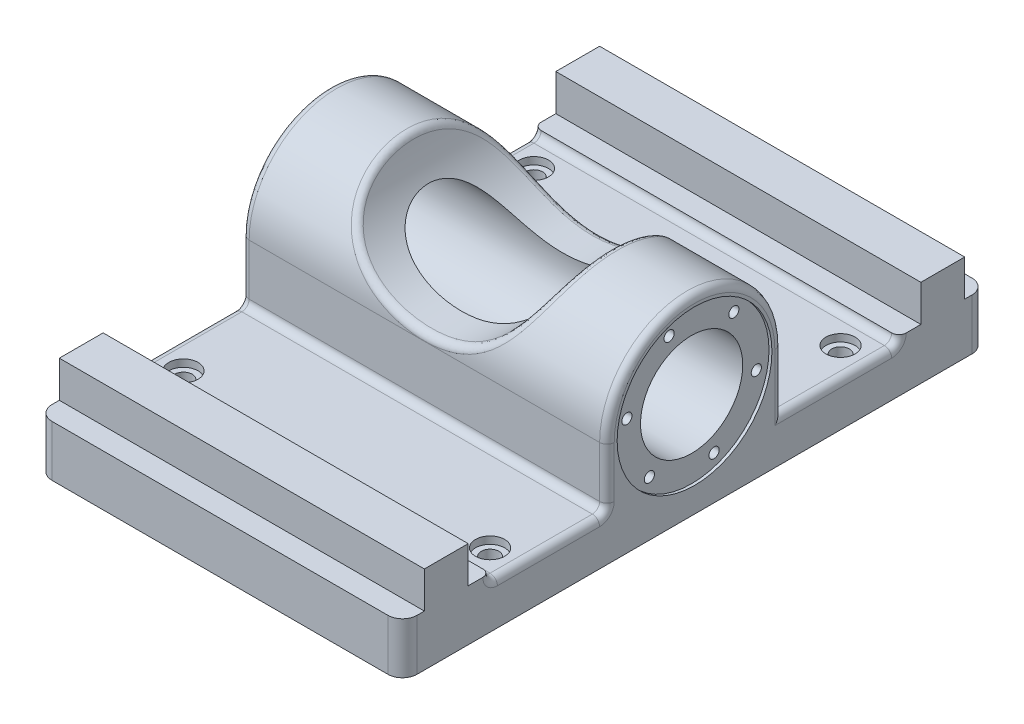
SolidWorks part; units mm, degrees
ref_plane "Front Plane" through (0, 0, 0) normal (0, 0, 1) x (1, 0, 0)
ref_plane "Top Plane" through (0, 0, 0) normal (0, 1, 0) x (1, 0, 0)
ref_plane "Right Plane" through (0, 0, 0) normal (1, 0, 0) x (0, 0, -1)
sketch "Sketch1" plane through (0, 0, 0) normal (0, 1, 0) x (1, 0, 0)
  line L1 (125, 200) -> (-125, 200)
  line L2 (125, 200) -> (125, -200)
  line L3 (125, -200) -> (-125, -200)
  line L4 (-125, 200) -> (-125, -200)
  line L5 (125, 200) -> (-125, -200) construction
  line L6 (125, -200) -> (-125, 200) construction
  point P0 (0, 0)
  dimension "D1" = 400
  dimension "D2" = 250
extrude "Boss-Extrude1" add sketch "Sketch1" along normal blind 30
sketch "Sketch2" plane through (0, 30, 0) normal (0, 1, 0) x (1, 0, 0)
  line L0 (-125, -200) -> (125, -200) construction
  line L1 (-125, -155) -> (125, -155)
  line L2 (-125, -155) -> (-125, -185)
  line L3 (-125, -185) -> (125, -185)
  line L4 (125, -155) -> (125, -185)
  line L5 (125, -200) -> (125, 200) construction
  line L6 (-125, 200) -> (-125, -200) construction
  dimension "D1" = 15
  dimension "D2" = 30
extrude "Boss-Extrude2" add sketch "Sketch2" along normal blind 30 contours L3 L4 L1 L2
sketch "Sketch3" plane through (0, 30, 0) normal (0, 1, 0) x (1, 0, 0)
  line L0 (-125, -200) -> (125, -200) construction
  line L1 (125, -140) -> (-125, -140)
  line L2 (125, -140) -> (125, -200)
  line L3 (125, -200) -> (-125, -200)
  line L4 (-125, -140) -> (-125, -200)
  line L5 (125, -200) -> (125, -185) construction
  line L6 (-125, -185) -> (-125, -200) construction
  dimension "D1" = 60
extrude "Boss-Extrude3" add sketch "Sketch3" along normal blind 5
mirror "Mirror1" about plane through (0, 0, 0) normal (0, 0, 1) of "Boss-Extrude3", "Boss-Extrude2"
sketch "Sketch4" plane through (-125, 0, 0) normal (-1, 0, 0) x (0, 0, 1)
  line L0 (60, 30) -> (-60, 30)
  line L1 (-140, 30) -> (140, 30) construction
  line L2 (-60, 30) -> (-60, 70)
  line L3 (60, 70) -> (60, 30)
  arc A0 (-60, 70) -> (60, 70) centre (0, 70) cw
  dimension "D1" = 40
  dimension "D2" = 130
extrude "Boss-Extrude4" add sketch "Sketch4" against normal up to surface (250 mm away) up to face at (125, 36.25, 0)
sketch "Sketch5" plane through (0, 0, 0) normal (1, 0, 0) x (0, 0, -1)
  circle A0 centre (0, 70) radius 35
  arc A1 (60, 70) -> (-60, 70) centre (0, 70) ccw construction
  dimension "D1" = 70
extrude "Cut-Extrude1" cut sketch "Sketch5" against normal through all both and the other way through all
sketch "Sketch6" plane through (-125, 0, 0) normal (-1, 0, 0) x (0, 0, 1)
  circle A0 centre (0, 70) radius 53
  arc A1 (60, 70) -> (-60, 70) centre (0, 70) ccw construction
  dimension "D1" = 106
extrude "Cut-Extrude2" cut sketch "Sketch6" against normal blind 2
sketch "Sketch7" plane through (-125, 0, 0) normal (-1, 0, 0) x (0, 0, 1)
  line L0 (0, 70) -> (45, 70) construction
  line L1 (0, 70) -> (15.3909, 112.2862) construction
  circle A0 centre (0, 70) radius 45 construction
  circle A1 centre (0, 70) radius 53 construction
  circle A2 centre (15.3909, 112.2862) radius 3.5
  dimension "D1" = 90
  dimension "D3" = 7
  dimension "D2" = 70
extrude "Cut-Extrude3" cut sketch "Sketch7" against normal blind 30
pattern_circular "CirPattern1" count 6 over 360 about axis through (0, 70, 0) along (1, 0, 0) of "Cut-Extrude3"
mirror "Mirror2" about plane through (0, 0, 0) normal (1, 0, 0) of "CirPattern1", "Cut-Extrude3", "Cut-Extrude2"
sketch "Sketch8" plane through (0, 30, 0) normal (0, 1, 0) x (1, 0, 0)
  line L0 (125, 60) -> (125, 140) construction
  line L1 (-125, 200) -> (125, 200) construction
  point P0 (105, 120)
  dimension "D1" = 20
  dimension "D2" = 80
hole_wizard "Hole1" positions "Sketch9" profile "Sketch10" legacy
sketch "Sketch9" plane through (0, 30, 0) normal (0, 1, 0) x (-1, 0, 0)
  point P0 (-105, -120)
sketch "Sketch10" plane through (105, 30, -120) normal (1, 0, 0) x (0, 0, 1)
  line L0 (0, 0) -> (0, 30)
  line L1 (0, 30) -> (6, 30)
  line L2 (6, 30) -> (6, 5)
  line L3 (6, 5) -> (10, 5)
  line L4 (10, 5) -> (10, 0)
  line L5 (10, 0) -> (0, 0)
  line L6 (0, 110) -> (0, -10) construction
  dimension "Diameter" = 12
  dimension "Depth" = 30
  dimension "C-Bore Diameter" = 20
  dimension "C-Bore Depth" = 5
pattern_linear "LPattern1" count 2 spacing 240 along (0, 0, 1) count 2 spacing 210 along (-1, 0, 0) of "Hole1"
sketch "Sketch11" plane through (0, 0, 0) normal (0, 0, 1) x (1, 0, 0)
  circle A0 centre (0, 145.04) radius 69.85
  dimension "D2" = 139.7
  dimension "D1" = 145.04
extrude "Cut-Extrude4" cut sketch "Sketch11" against normal through all both and the other way through all
fillet "Fillet1" radius 10 4 edges at (-125, 17.5, -200) (125, 17.5, -200) (-125, 17.5, 200) (125, 17.5, 200)
fillet "Fillet2" radius 5 14 edges at (125, 50, -60) (-125, 50, -60) (125, 130, 0) (-125, 130, 0) (-125, 30, 100) (125, 50, 60) (-125, 50, 60) (-67.7822, 128.1702, 14.7046) (0, 30, 140) (-125, 30, -100) (0, 30, -140) (125, 30, -100) (125, 30, 100) (0, 30, 60)
